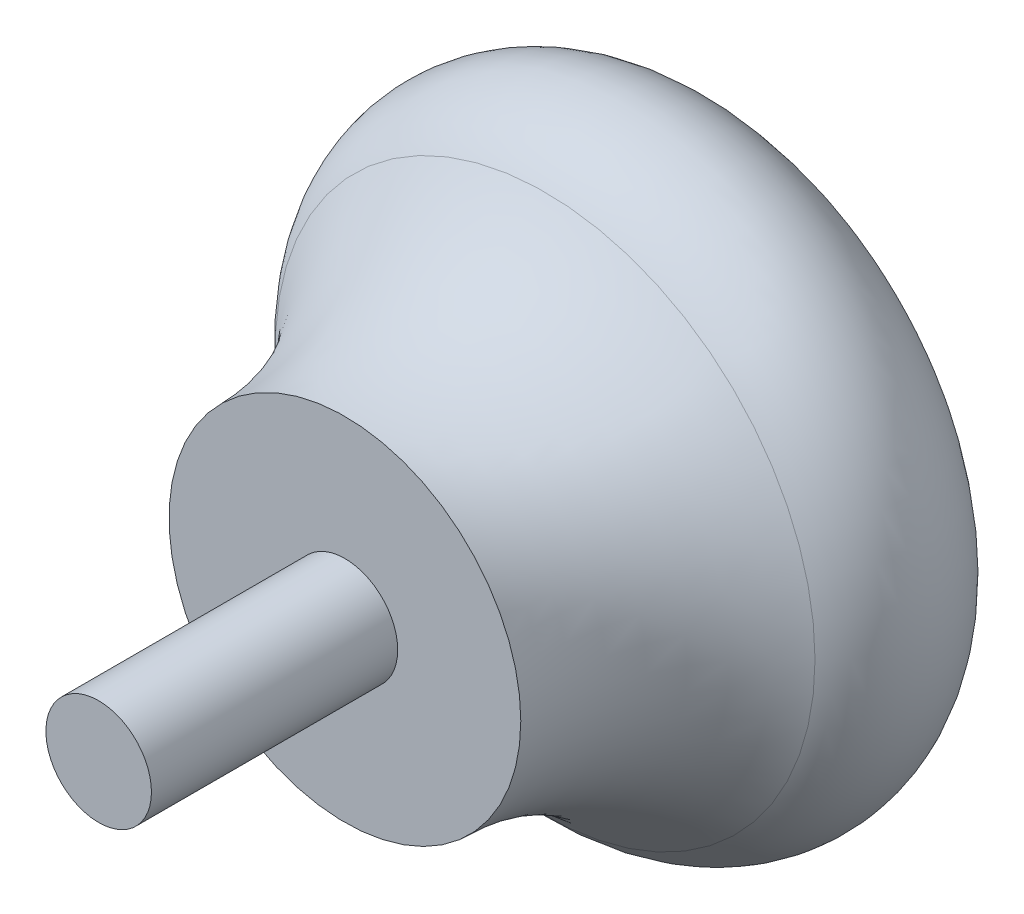
SolidWorks part; units mm, degrees
material "Cast Alloy Steel"
ref_plane "Front Plane" through (0, 0, 0) normal (0, 0, 1) x (1, 0, 0)
ref_plane "Top Plane" through (0, 0, 0) normal (0, 1, 0) x (1, 0, 0)
ref_plane "Right Plane" through (0, 0, 0) normal (1, 0, 0) x (0, 0, -1)
sketch "Sketch1" plane through (0, 0, 0) normal (0, 0, 1) x (1, 0, 0)
  circle A0 centre (0, 0) radius 10
  dimension "D1" = 20
extrude "Boss-Extrude1" add sketch "Sketch1" along normal blind 4
sketch "Sketch2" plane through (0, 0, 4) normal (0, 0, 1) x (1, 0, 0)
  circle A0 centre (0, 0) radius 5
  dimension "D1" = 10
extrude "Boss-Extrude2" add sketch "Sketch2" along normal blind 7
sketch "Sketch3" plane through (0, 0, 11) normal (0, 0, 1) x (1, 0, 0)
  circle A0 centre (0, 0) radius 1.5
  dimension "D1" = 3
extrude "Boss-Extrude3" add sketch "Sketch3" along normal blind 7
fillet "Fillet4" radius 7.4 1 edges at (5, 0, 4)
fillet "Fillet15" radius 4.2 1 edges at (10, 0, 0)
fillet "Fillet16" radius 3 1 edges at (10, 0, 4)
